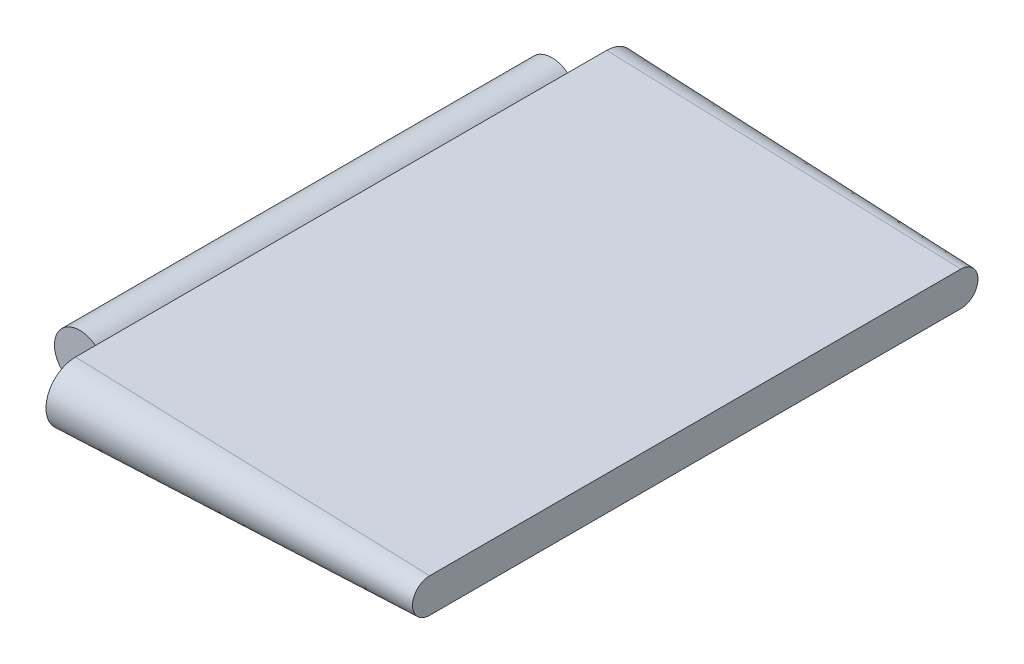
SolidWorks part; units mm, degrees
material "1060 Alloy"
ref_plane "Front Plane" through (0, 0, 0) normal (0, 0, 1) x (1, 0, 0)
ref_plane "Top Plane" through (0, 0, 0) normal (0, 1, 0) x (1, 0, 0)
ref_plane "Right Plane" through (0, 0, 0) normal (1, 0, 0) x (0, 0, -1)
sketch "Sketch1" plane through (0, 0, 0) normal (1, 0, 0) x (0, 0, -1)
  line L0 (-112.5, 0) -> (112.5, 0) construction
  line L1 (-112.5, 12.5) -> (112.5, 12.5)
  line L2 (-112.5, -12.5) -> (112.5, -12.5)
  arc A0 (-112.5, 12.5) -> (-112.5, -12.5) centre (-112.5, 0) ccw
  arc A1 (112.5, -12.5) -> (112.5, 12.5) centre (112.5, 0) ccw
  point P2 (0, 0)
  dimension "D1" = 225
  dimension "D2" = 25
extrude "Boss-Extrude1" add sketch "Sketch1" along normal blind 150 draft 2 contours L2 A1 L1 A0
sketch "Sketch3" plane through (0, 0, 0) normal (0, 0, 1) x (1, 0, 0)
  circle A0 centre (-10.7133, 0) radius 10.7133
extrude "Boss-Extrude3" add sketch "Sketch3" along normal blind 100 and the other way blind 100 separate body
